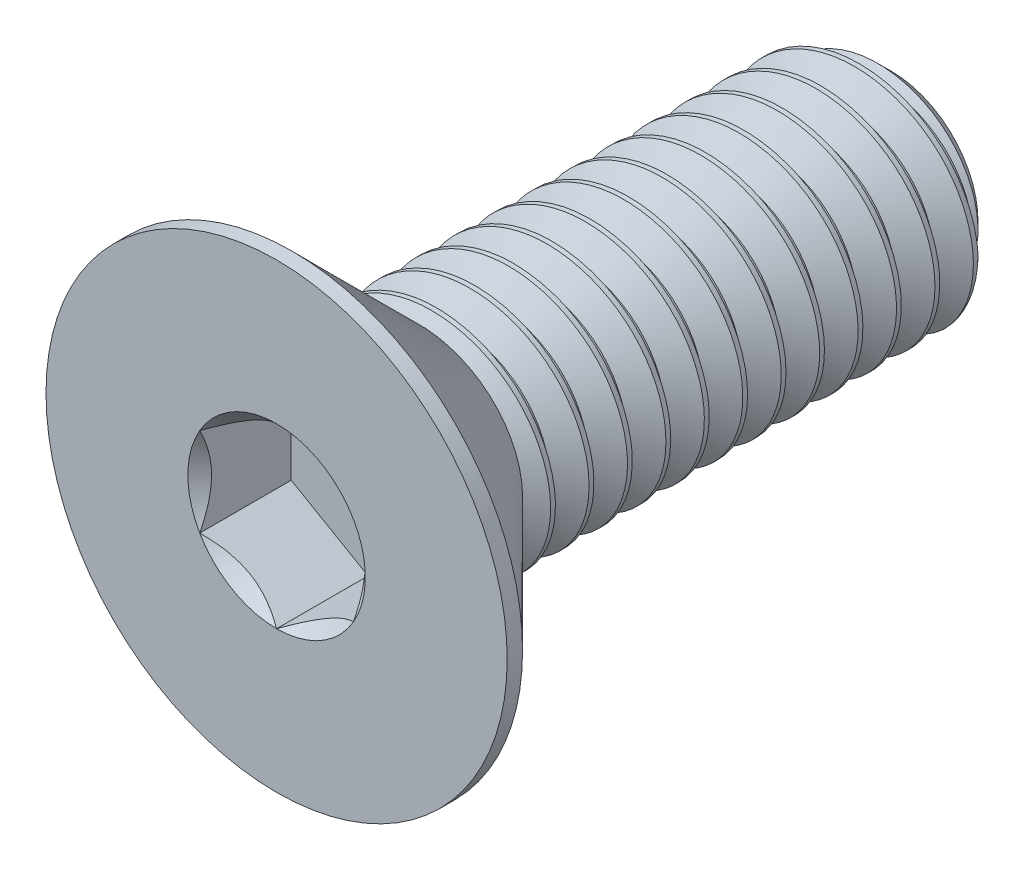
SolidWorks part; units mm, degrees
material "Plain Carbon Steel"
ref_plane "Front" through (0, 0, 0) normal (0, 0, 1) x (1, 0, 0)
ref_plane "Top" through (0, 0, 0) normal (0, 1, 0) x (1, 0, 0)
ref_plane "Right" through (0, 0, 0) normal (1, 0, 0) x (0, 0, -1)
sketch "Sketch1" plane through (0, 0, 0) normal (1, 0, 0) x (0, 0, -1)
  line L0 (0, 3) -> (0.2, 3) construction
  line L1 (0.2, 3) -> (1.7, 1.5) construction
  line L2 (0, 1.5) -> (8, 1.5)
  line L3 (8, 1.5) -> (8, 0)
  line L4 (8, 0) -> (0, 0)
  line L5 (0, 0) -> (0, 3) construction
  line L6 (0, 3) -> (0, -3) construction
  line L7 (8, 1.5) -> (8, -1.5) construction
  line L8 (0, -3) -> (0.2, -3) construction
  line L9 (0.2, -3) -> (1.7, -1.5) construction
  line L11 (0, 1.5) -> (0, 0)
  line L12 (1.7, 1.5) -> (1.7, 0) construction
revolve "Revolve1" add sketch "Sketch1" angle 360 mid plane about L4
sketch "Sketch3" plane through (0, 0, -8) normal (0, 0, -1) x (-1, 0, 0)
  circle A0 centre (0, 0) radius 1.5
curve "Helix/Spiral1" pitch 0.5 height 8 radius 1.5 centre (0, 0, -8) axis (0, 0, 1) start towards (0, 1, 0)
sketch "Sketch2" plane through (0, 0, 0) normal (1, 0, 0) x (0, 0, -1)
  line L0 (8, 1.5) -> (8.4375, 1.5)
  line L1 (8.4375, 1.5) -> (8.25, 1.1752)
  line L2 (8.25, 1.1752) -> (8.1875, 1.1752)
  line L3 (8.1875, 1.1752) -> (8, 1.5)
  line L4 (8.0938, 1.3376) -> (8.3438, 1.3376) construction
  dimension "D1" = 60
  dimension "D2" = 0.0625
  dimension "D3" = 0.25
chamfer "Chamfer1" distance 0.375 angle 45 1 edges at (0, 1.5, -8)
sweep "Cut-Sweep1" cut profiles "Sketch2" path "Helix/Spiral1" align with end faces yes
sketch "Sketch7" plane through (0, 0, 0) normal (1, 0, 0) x (0, 0, -1)
  line L0 (0, 3) -> (0.2, 3) construction
  line L1 (0.2, 3) -> (1.7, 1.5) construction
  line L2 (0, 3) -> (0.2, 3)
  line L3 (0.2, 3) -> (1.7, 1.5)
  line L4 (1.7, 1.5) -> (1.7, 0) construction
  line L5 (1.7, 1.5) -> (1.7, 0)
  line L7 (0, 0) -> (0, 3) construction
  line L8 (0, 0) -> (0, 3)
  line L9 (0, 0) -> (1.7, 0)
  line L10 (3.3, 0) -> (-3.3, 0) construction
revolve "Revolve2" add sketch "Sketch7" angle 360 mid plane about L9
ref_plane "Plane1" through (0, 0, -1.7) normal (0, 0, 1) x (1, 0, 0)
sketch "Sketch8" plane through (0, 0, -1.7) normal (0, 0, 1) x (1, 0, 0)
  circle A0 centre (0, 0) radius 1.5
extrude "Boss-Extrude1" add sketch "Sketch8" against normal through all draft 45
sketch "Sketch5" plane through (0, 0, 0) normal (0, 0, 1) x (1, 0, 0)
  line L1 (1, -0.5774) -> (1, 0.5774)
  line L2 (1, 0.5774) -> (0, 1.1547)
  line L3 (0, 1.1547) -> (-1, 0.5774)
  line L4 (-1, 0.5774) -> (-1, -0.5774)
  line L5 (-1, -0.5774) -> (0, -1.1547)
  line L6 (0, -1.1547) -> (1, -0.5774)
  circle A0 centre (0, 0) radius 1 construction
  dimension "Hex" = 2
extrude "Cut-Extrude2" cut sketch "Sketch5" against normal blind 1.19
sketch "Sketch6" plane through (0, 0, 0) normal (0, 0, 1) x (1, 0, 0)
  circle A0 centre (0, 0) radius 1.1547
extrude "Cut-Extrude3" cut sketch "Sketch6" against normal blind 1.19 draft 45
sketch "Sketch9" [suppressed] plane through (0, 0, -5.5) normal (0, 0, 1) x (1, 0, 0)
  circle A1 centre (0, 0) radius 5
  circle A2 centre (0, 0) radius 5
  point P0 (0, 5)
  dimension "D1" = 0
extrude "Boss-Extrude2" [suppressed] add sketch "Sketch9" against normal offset from surface (18.5 mm away) 26 up to face at (0, 1.125, -8)
fillet "Fillet1" [suppressed] radius 0.3
sketch "Sketch10" plane through (0, 0, 0) normal (1, 0, 0) x (0, 0, -1)
  line L0 (8, 1.5) -> (8, -1.5) construction
  point P0 (7.25, -1.5)
  dimension "D1" = 0.75
equation "\"D3@Helix/Spiral1\" = \"Lg@Sketch1\""
equation "\"D2@Sketch2\" = \"D4@Helix/Spiral1\" * .125"
equation "\"D3@Sketch2\" = \"D4@Helix/Spiral1\" * .5"
equation "\"D1@Chamfer1\" = \"D4@Helix/Spiral1\" * .75"
equation "\"D1@Cut-Extrude2\" = \"Head Ht@Sketch1\" * .7"
equation "\"D1@Sketch10\" = \"D4@Helix/Spiral1\" * 1.5"
equation "\"D1@Cut-Extrude3\" = \"D1@Cut-Extrude2\""
equation "\"D1@Fillet1\" = \"Dia@Sketch1\" * .1"
